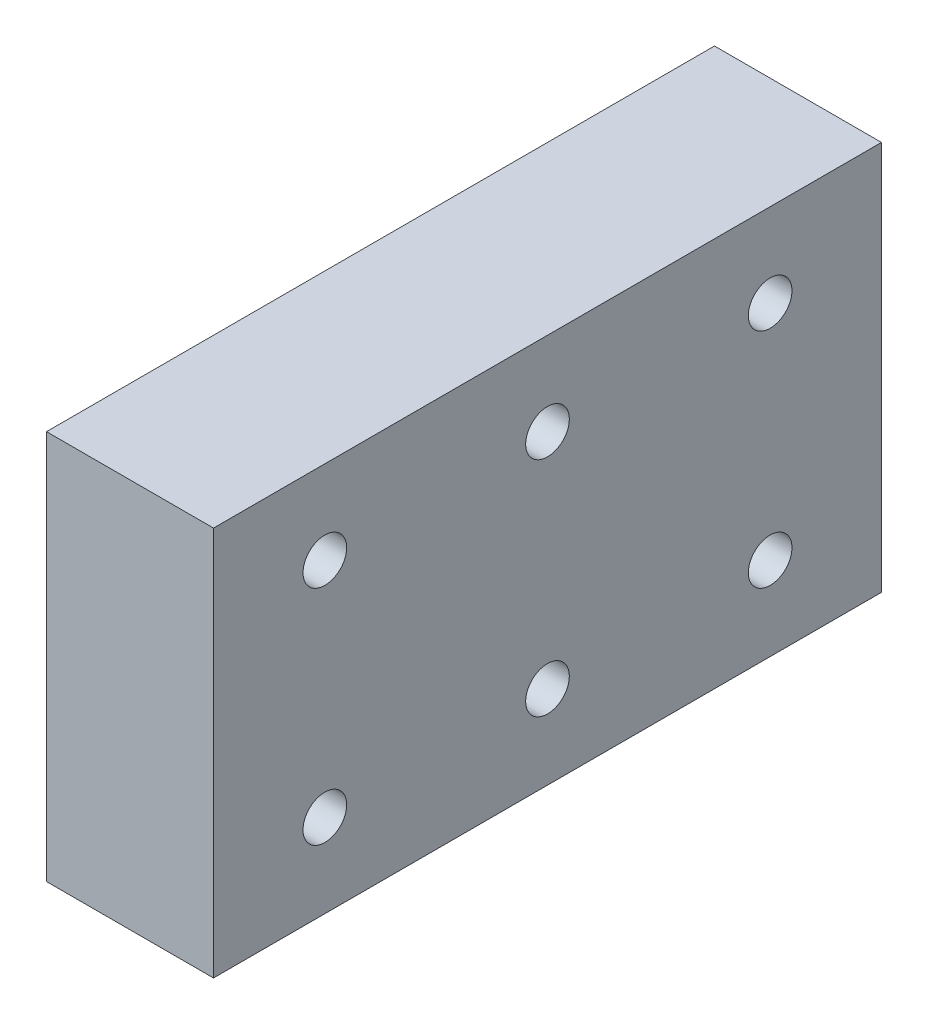
SolidWorks part; units mm, degrees
material "PET"
ref_plane "Front Plane" through (0, 0, 0) normal (0, 0, 1) x (1, 0, 0)
ref_plane "Top Plane" through (0, 0, 0) normal (0, 1, 0) x (1, 0, 0)
ref_plane "Right Plane" through (0, 0, 0) normal (1, 0, 0) x (0, 0, -1)
sketch "Sketch1" plane through (0, 0, 0) normal (0, 0, 1) x (1, 0, 0)
  line L1 (0, 0) -> (19.05, 0)
  line L2 (0, 0) -> (0, 44.45)
  line L3 (0, 44.45) -> (19.05, 44.45)
  line L4 (19.05, 0) -> (19.05, 44.45)
  dimension "D1" = 44.45
  dimension "D2" = 19.05
extrude "Boss-Extrude1" add sketch "Sketch1" along normal blind 76.2
sketch "Sketch2" plane through (19.05, 0, 0) normal (1, 0, 0) x (0, 0, -1)
  line L0 (-76.2, 0) -> (0, 0) construction
  line L1 (-76.2, 0) -> (-76.2, 44.45) construction
  circle A0 centre (-63.5, 9.525) radius 2.4892
  circle A1 centre (-38.1, 9.525) radius 2.4892
  circle A2 centre (-12.7, 9.525) radius 2.4892
  circle A3 centre (-63.5, 34.925) radius 2.4892
  circle A4 centre (-38.1, 34.925) radius 2.4892
  circle A5 centre (-12.7, 34.925) radius 2.4892
  dimension "D1" = 4.9784
  dimension "D2" = 9.525
  dimension "D3" = 12.7
  dimension "D4" = 3
  dimension "D5" = 2
extrude "Cut-Extrude1" cut sketch "Sketch2" against normal through all
